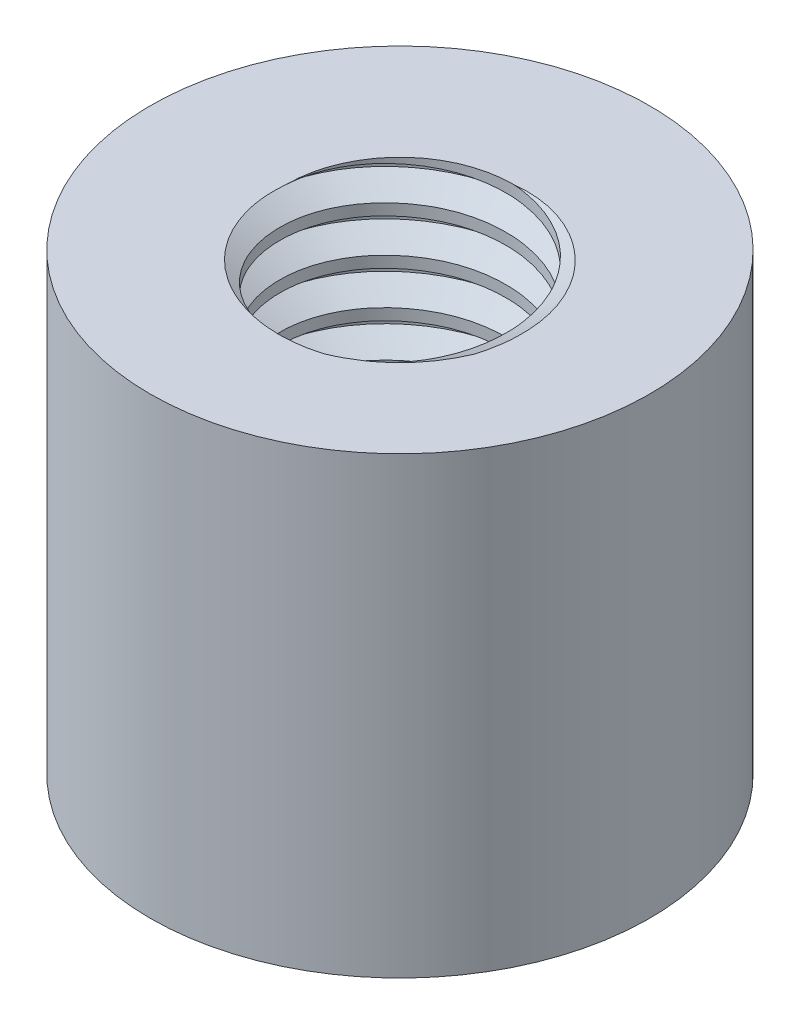
SolidWorks part; units mm, degrees
ref_plane "Front Plane" through (0, 0, 0) normal (0, 0, 1) x (1, 0, 0)
ref_plane "Top Plane" through (0, 0, 0) normal (0, 1, 0) x (1, 0, 0)
ref_plane "Right Plane" through (0, 0, 0) normal (1, 0, 0) x (0, 0, -1)
sketch "Sketch1" plane through (0, 0, 0) normal (0, 1, 0) x (1, 0, 0)
  circle A2 centre (0, 0) radius 2.75
  dimension "D1" = 5.5
extrude "Boss-Extrude1" add sketch "Sketch1" along normal blind 5
hole_wizard "M3x0.5 Tapped Hole1" positions "Sketch4" profile "Sketch5" tap size "M3x0.5" standard "ANSI Metric" end condition through all
sketch "Sketch4" plane through (0, 5, 0) normal (0, 1, 0) x (1, 0, 0)
  point P0 (0, 0)
cosmetic thread "Hole Thread1"
sketch "Sketch5" plane through (0, 5, 0) normal (1, 0, 0) x (0, 0, 1)
  line L0 (0, 0) -> (0, 5)
  line L1 (0, 5) -> (1.25, 5)
  line L2 (1.25, 5) -> (1.25, 0)
  line L5 (1.25, 0) -> (0, 0)
  line L11 (0, -6.35) -> (0, 107.95) construction
  dimension "Thru Tap Drill Dia." = 2.5
  dimension "Thru Tap Drill Depth" = 5
thread "Thread1" pitch 0.5 method cut profile "Thread Profile1" start angle 0, offset 1, length 0, pitch 0.5, diameter 2.5
ref_plane "Plane1" through (-1.25, 6, 0) normal (0, 0, 1) x (-1, 0, 0)
sketch "Thread Profile1" plane through (-1.25, 6, 0) normal (0, 0, 1) x (-1, 0, 0)
  line L0 (0, 0) -> (0, 0.5) construction
  line L1 (0, 0) -> (0.2706, 0.1562)
  line L2 (0.2706, 0.1562) -> (0.2706, 0.2187)
  line L3 (0.2706, 0.2187) -> (0, 0.375)
  line L4 (0.2706, 0.1875) -> (0, 0.1875) construction
  line L11 (0, 0) -> (0, 0.375)
  point P2 (0, 0)
  dimension "Pitch" = 0.5
  dimension "Profile_Angle" = 60
  dimension "Profile_Land" = 0.0625
  dimension "Profile_Height" = 0.2706
